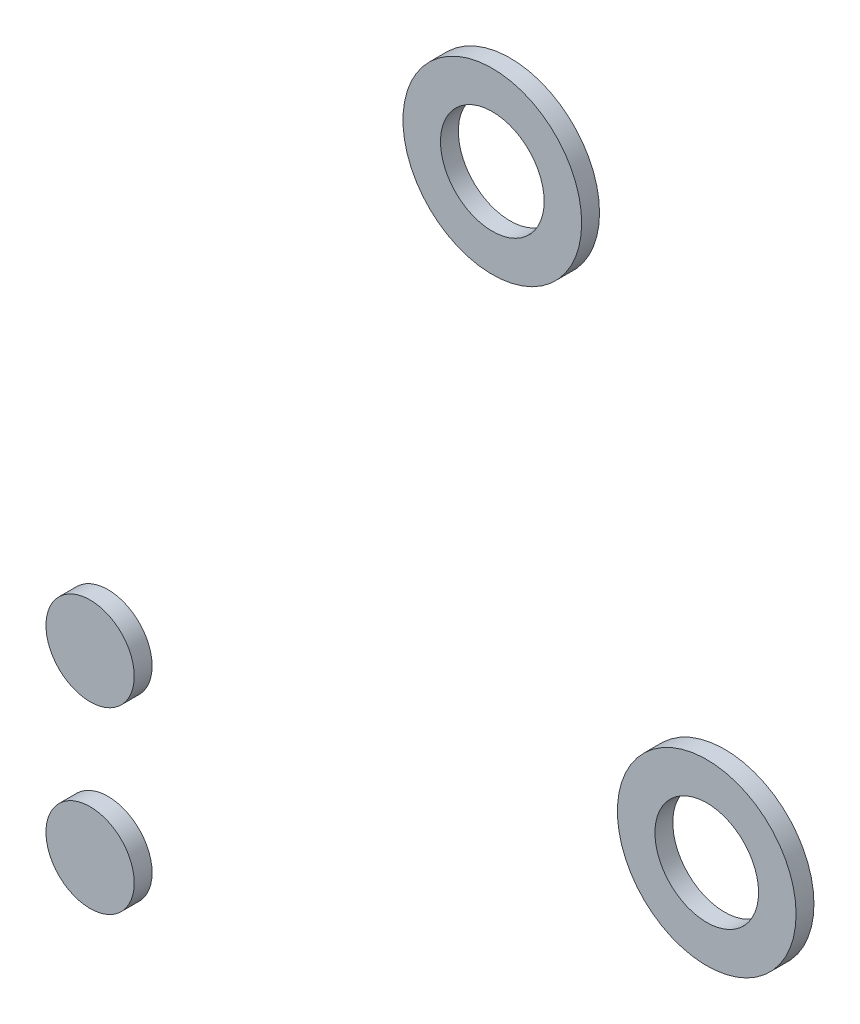
SolidWorks part; units mm, degrees
ref_plane "前视基准面" through (0, 0, 0) normal (0, 0, 1) x (1, 0, 0)
ref_plane "上视基准面" through (0, 0, 0) normal (0, 1, 0) x (1, 0, 0)
ref_plane "右视基准面" through (0, 0, 0) normal (1, 0, 0) x (0, 0, -1)
sketch "草图6" plane through (0, 0, 0) normal (0, 0, 1) x (1, 0, 0)
  circle A0 centre (22.51, 44.51) radius 2.9
  circle A1 centre (34.51, 17.01) radius 2.9
  circle A2 centre (0, 10.02) radius 2.47
  circle A3 centre (0, 0) radius 2.47
  circle A4 centre (22.51, 44.51) radius 5
  circle A5 centre (34.51, 17.01) radius 5
  dimension "D2" = 10
  dimension "D3" = 10
  dimension "D1" = 10.02
extrude "凸台-拉伸5" add sketch "草图6" along normal blind 1 separate body
